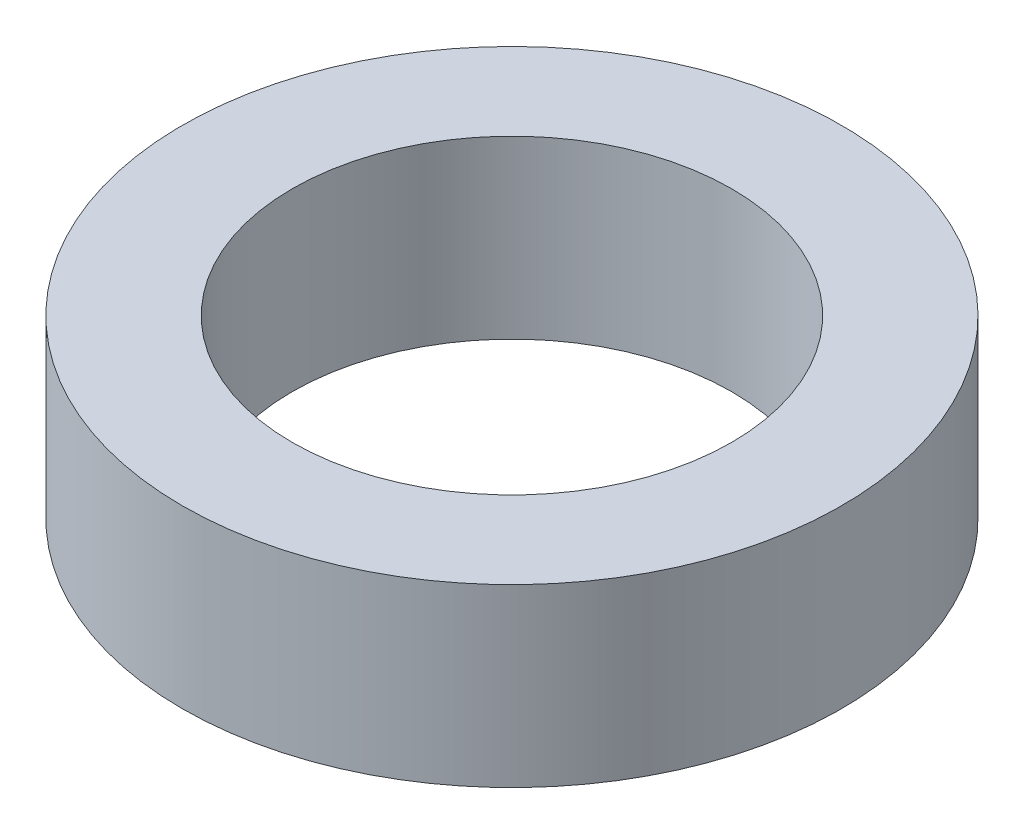
SolidWorks part; units mm, degrees
ref_plane "Front Plane" through (0, 0, 0) normal (0, 0, 1) x (1, 0, 0)
ref_plane "Top Plane" through (0, 0, 0) normal (0, 1, 0) x (1, 0, 0)
ref_plane "Right Plane" through (0, 0, 0) normal (1, 0, 0) x (0, 0, -1)
sketch "Sketch1" plane through (0, 0, 0) normal (0, 1, 0) x (1, 0, 0)
  circle A0 centre (0, 0) radius 7.5
  dimension "D1" = 15
extrude "Boss-Extrude1" add sketch "Sketch1" along normal blind 4
sketch "Sketch2" plane through (0, 4, 0) normal (0, 1, 0) x (1, 0, 0)
  circle A0 centre (0, 0) radius 5
  dimension "D1" = 10
extrude "Cut-Extrude1" cut sketch "Sketch2" against normal blind 10
